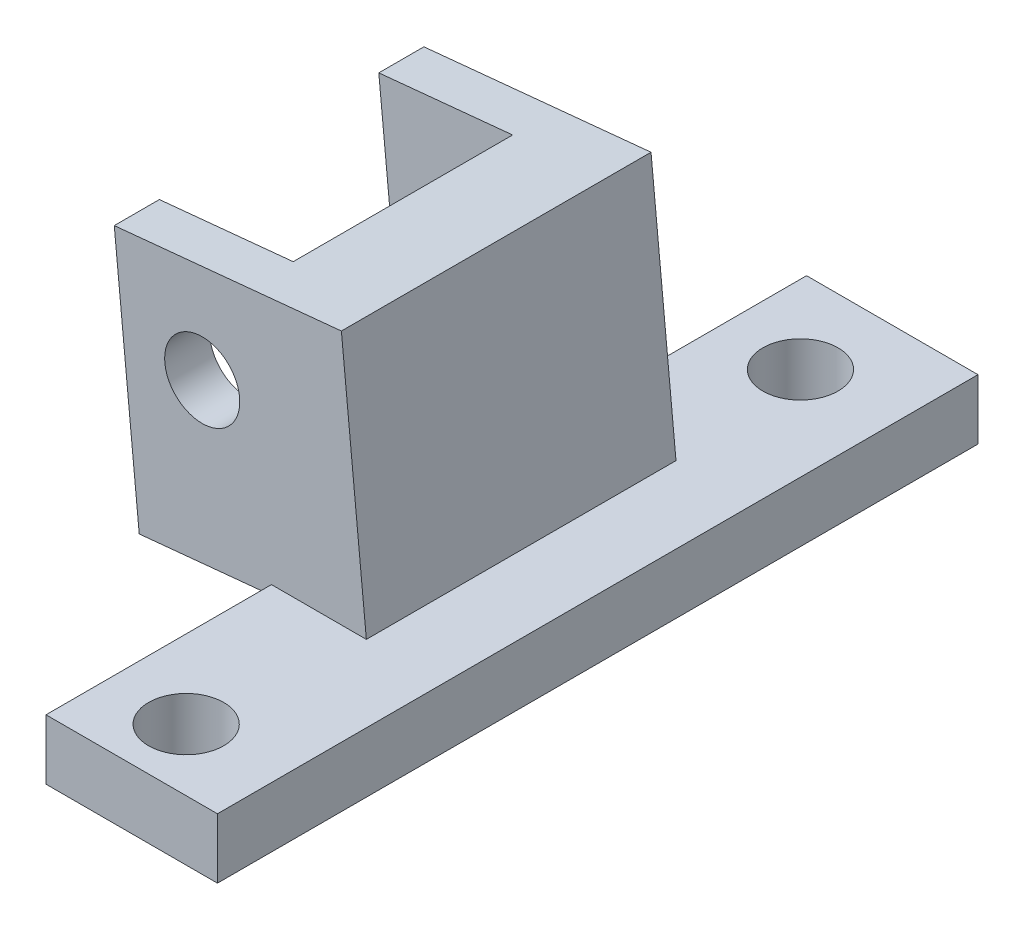
SolidWorks part; units mm, degrees
ref_plane "Front Plane" through (0, 0, 0) normal (0, 0, 1) x (1, 0, 0)
ref_plane "Top Plane" through (0, 0, 0) normal (0, 1, 0) x (1, 0, 0)
ref_plane "Right Plane" through (0, 0, 0) normal (1, 0, 0) x (0, 0, -1)
sketch "Sketch1" plane through (0, 0, 0) normal (0, 0, 1) x (1, 0, 0)
  line L0 (476.9237, 158.5913) -> (479.0335, 137.0791)
  line L1 (479.0335, 137.0791) -> (498.2247, 138.9613)
  line L2 (498.2247, 138.9613) -> (496.115, 160.4735)
  line L3 (496.115, 160.4735) -> (476.9237, 158.5913)
  line L4 (485.2846, 141.5205) -> (469.8952, 140.0112) construction
  line L5 (485.2846, 141.5205) -> (469.8952, 140.0112)
  arc A0 (489.9044, 158.7414) -> (483.4252, 160.4795) centre (484.3549, 151) ccw construction
  arc A1 (491.3026, 144.4842) -> (489.9044, 158.7414) centre (484.3549, 151) ccw construction
  arc A2 (485.2846, 141.5205) -> (491.3026, 144.4842) centre (484.3549, 151) ccw construction
  arc A3 (489.9044, 158.7414) -> (483.4252, 160.4795) centre (484.3549, 151) ccw
  arc A4 (491.3026, 144.4842) -> (489.9044, 158.7414) centre (484.3549, 151) ccw
  arc A5 (485.2846, 141.5205) -> (491.3026, 144.4842) centre (484.3549, 151) ccw
  dimension "D1" = 6.35
  dimension "D2" = 3.81
extrude "Boss-Extrude5" add sketch "Sketch1" against normal blind 22.352 contours A5 L5 L0 L1 L2 L3 A3 A4 region at (482.0029, 140.8922, 0)
sketch "Sketch2" plane through (0, 0, -22.352) normal (0, 0, -1) x (-1, 0, 0)
  line L0 (-488.2317, 159.7003) -> (-476.9237, 158.5913)
  line L1 (-476.9237, 158.5913) -> (-478.6616, 140.8709)
  line L2 (-478.6616, 140.8709) -> (-485.2846, 141.5205)
  arc A0 (-485.2846, 141.5205) -> (-488.2317, 159.7003) centre (-484.3549, 151) cw
  circle A1 centre (-484.3549, 151) radius 3.175 construction
  circle A2 centre (-484.3549, 151) radius 3.175
  circle A3 centre (-484.3549, 151) radius 3.175
  arc M5 (-485.2846, 141.5205) -> (-488.2317, 159.7003) centre (-484.3549, 151) cw
  line M10 (-478.6616, 140.8709) -> (-485.2846, 141.5205)
extrude "Boss-Extrude7" add sketch "Sketch2" against normal blind 3.81 contours L1 L0 A2 M5 M10 region at (482.6025, 158.8937, -22.352)
sketch "Sketch3" plane through (0, 0, 0) normal (0, 0, 1) x (1, 0, 0)
  line L0 (476.9237, 158.5913) -> (479.0335, 137.0791)
  line L1 (479.0335, 137.0791) -> (498.2247, 138.9613)
  line L2 (498.2247, 138.9613) -> (496.115, 160.4735)
  line L3 (496.115, 160.4735) -> (476.9237, 158.5913)
  circle A0 centre (484.3549, 151) radius 3.175 construction
  circle A1 centre (484.3549, 151) radius 3.175
  circle A2 centre (484.3549, 151) radius 3.175
  arc M6 (488.2317, 159.7003) -> (485.2846, 141.5205) centre (484.3549, 151) cw
  line M7 (485.2846, 141.5205) -> (478.6616, 140.8709)
  line M8 (478.6616, 140.8709) -> (479.0335, 137.0791)
  line M9 (479.0335, 137.0791) -> (498.2247, 138.9613)
  line M10 (498.2247, 138.9613) -> (496.115, 160.4735)
  line M11 (496.115, 160.4735) -> (488.2317, 159.7003)
extrude "Boss-Extrude8" add sketch "Sketch3" along normal blind 3.81 contours L3 L0 A1 M6 M7 | M11 M6 M7 M8 M9 M10 region at (482.6025, 158.8937, 0) region at (482.0029, 140.8922, 0)
ref_plane "Plane1" through (0, 138.9613, 0) normal (0, 1, 0) x (1, 0, 0)
sketch "Sketch4" plane through (0, 138.9613, 0) normal (0, 1, 0) x (1, 0, 0)
  line L1 (490.2062, 41.402) -> (504.6925, 41.402)
  line L2 (490.2062, 41.402) -> (490.2062, -22.86)
  line L3 (490.2062, -22.86) -> (504.6925, -22.86)
  line L4 (504.6925, 41.402) -> (504.6925, -22.86)
  dimension "D1" = 19.05
  dimension "D2" = 19.05
extrude "Boss-Extrude9" add sketch "Sketch4" against normal blind 5.08
sketch "Sketch6" plane through (0, 138.9613, 0) normal (0, 1, 0) x (1, 0, 0)
  line L0 (504.6925, -22.86) -> (504.6925, 41.402) construction
  line L1 (490.2062, -3.81) -> (490.2062, -22.86) construction
  line L2 (490.2062, 41.402) -> (490.2062, 22.352) construction
  circle A0 centre (496.8102, -17.6212) radius 3.175
  circle A1 centre (496.8102, 34.2816) radius 3.175
  dimension "D1" = 6.35
  dimension "D2" = 6.35
  dimension "D3" = 14.4863
  dimension "D4" = 6.604
  dimension "D5" = 6.604
extrude "Cut-Extrude1" cut sketch "Sketch6" against normal blind 6.35
